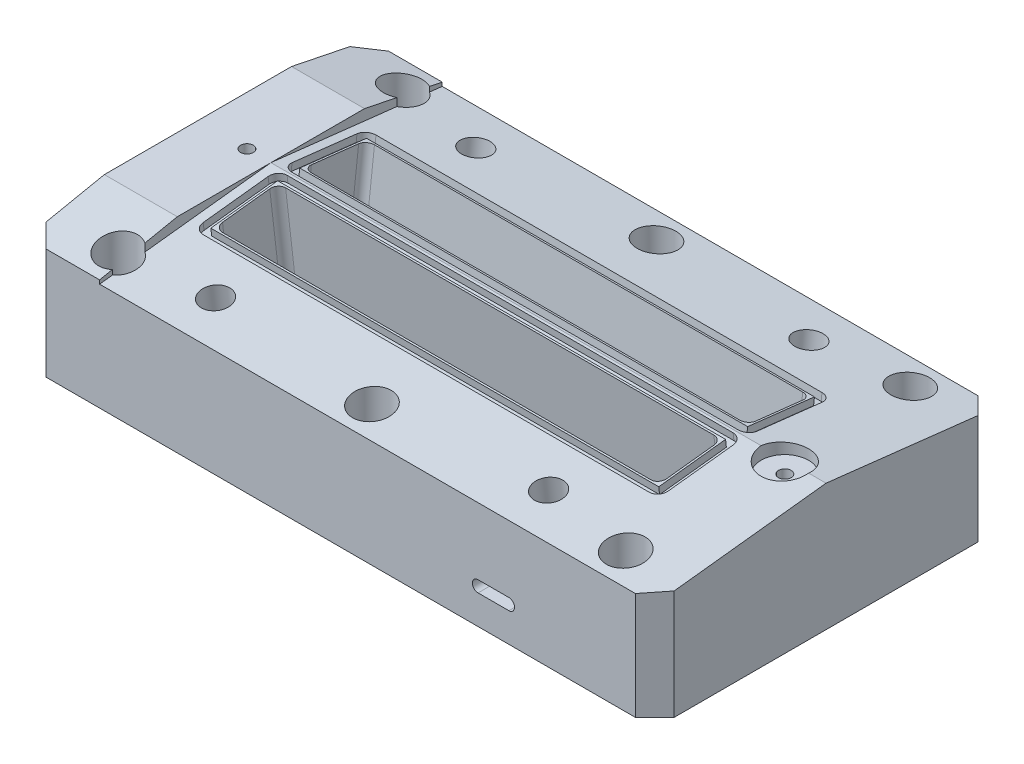
SolidWorks part; units mm, degrees
material "Custom Plastic"
ref_plane "Front Plane" through (0, 0, 0) normal (0, 0, 1) x (1, 0, 0)
ref_plane "Top Plane" through (0, 0, 0) normal (0, 1, 0) x (1, 0, 0)
ref_plane "Right Plane" through (0, 0, 0) normal (1, 0, 0) x (0, 0, -1)
sketch "Sketch1" plane through (0, 0, 0) normal (0, 1, 0) x (1, 0, 0)
  line L1 (0, 0) -> (198, 0)
  line L2 (0, 0) -> (0, 108)
  line L3 (0, 108) -> (198, 108)
  line L4 (198, 0) -> (198, 108)
  dimension "D1" = 198
  dimension "D2" = 108
extrude "Boss-Extrude1" add sketch "Sketch1" along normal blind 40
ref_plane "Left" through (198, 0, 0) normal (1, 0, 0) x (0, 0, -1)
ref_plane "Bot" through (0, 40, 0) normal (0, 1, 0) x (1, 0, 0)
ref_plane "der loco" through (0, 0, -52) normal (0, 0, -1) x (-1, 0, 0)
sketch "Sketch4" plane through (0, 0, 0) normal (0, 1, 0) x (1, 0, 0)
  line L0 (0, 108) -> (0, 0) construction
  line L1 (8.5, 31.5) -> (189.5, 31.5)
  line L2 (8.5, 31.5) -> (8.5, 76.5)
  line L3 (8.5, 76.5) -> (189.5, 76.5)
  line L4 (189.5, 31.5) -> (189.5, 76.5)
  line L5 (0, 0) -> (198, 0) construction
  dimension "D1" = 181
  dimension "D2" = 8.5
  dimension "D3" = 45
  dimension "D4" = 31.5
extrude "Cut-Extrude2" cut sketch "Sketch4" along normal blind 10 contours L2 L1 L4 L3
ref_plane "Plane32" through (0, 10, 0) normal (0, -1, 0) x (-1, 0, 0)
sketch "Sketch5" plane through (198, 0, 0) normal (1, 0, 0) x (0, 0, -1)
  line L0 (54, 40) -> (108, 33.8284)
  line L1 (0, 40) -> (108, 40) construction
  line L2 (108, 33.8284) -> (108, 40)
  line L3 (108, 40) -> (54, 40)
  line L4 (108, 40) -> (108, 0) construction
  dimension "D1" = 6.52
  dimension "D2" = 54
extrude "Cut-Extrude3" cut sketch "Sketch5" against normal blind 175
ref_plane "Plane24" through (0, 10, 0) normal (0, -1, 0) x (-1, 0, 0)
sketch "Sketch53" plane through (0, 10, 0) normal (0, -1, 0) x (-1, 0, 0)
  line L0 (-8.5, 51.5) -> (-8.5, 31.5)
  line L1 (-8.5, 76.5) -> (-8.5, 31.5) construction
  line L2 (-8.5, 31.5) -> (-39.5, 31.5)
  line L3 (-8.5, 31.5) -> (-189.5, 31.5) construction
  line L4 (-39.5, 31.5) -> (-8.5, 51.5)
  line L5 (-8.5, 54) -> (-189.5, 54) construction
  line L6 (-189.5, 31.5) -> (-189.5, 76.5) construction
  line L7 (-8.5, 56.5) -> (-8.5, 76.5)
  line L8 (-8.5, 76.5) -> (-39.5, 76.5)
  line L9 (-39.5, 76.5) -> (-8.5, 56.5)
  line L10 (-99, 76.5) -> (-99, 31.5) construction
  line L11 (-8.5, 76.5) -> (-189.5, 76.5) construction
  line L12 (-8.5, 31.5) -> (-189.5, 31.5) construction
  line L13 (-158.5, 76.5) -> (-189.5, 56.5)
  line L14 (-189.5, 76.5) -> (-158.5, 76.5)
  line L15 (-189.5, 56.5) -> (-189.5, 76.5)
  line L16 (-158.5, 31.5) -> (-189.5, 51.5)
  line L17 (-189.5, 31.5) -> (-158.5, 31.5)
  line L18 (-189.5, 51.5) -> (-189.5, 31.5)
  dimension "D1" = 31
  dimension "D2" = 20
extrude "Boss-Extrude11" add sketch "Sketch53" along normal up to surface (10 mm away) up to face at (99, 0, -54)
ref_plane "izq loco" through (0, 0, -57) normal (0, 0, -1) x (-1, 0, 0)
sketch "Sketch18" plane through (198, 0, 0) normal (1, 0, 0) x (0, 0, -1)
  line L0 (0, 33.8284) -> (0, 40)
  line L1 (0, 40) -> (0, 0) construction
  line L2 (0, 40) -> (54, 40)
  line L3 (54, 40) -> (0, 33.8284)
  line L4 (0, 40) -> (54, 40) construction
  dimension "D1" = 54
  dimension "D2" = 6.52
extrude "Cut-Extrude12" cut sketch "Sketch18" against normal up to surface (175 mm away) up to face at (23, 37.9428, -90)
sketch "Sketch60" plane through (0, 0, 0) normal (0, 1, 0) x (1, 0, 0)
  point P0 (8.5, 31.5)
  point P1 (39.5, 31.5)
  point P2 (8.5, 76.5)
  point P6 (39.5, 76.5)
  dimension "D1" = 20
  dimension "D2" = 31
  dimension "D3" = 20
  dimension "D4" = 31
ref_axis "Axis6" through (8.5, 0, -31.5) along (1, 0, 0)
sketch "Sketch69" plane through (0, 10, 0) normal (0, -1, 0) x (-1, 0, 0)
  point P0 (-39.5, 56.5)
  point P1 (-8.5, 51.5)
  point P2 (-38.5, 51.5)
  point P3 (-8.5, 56.5)
  dimension "D1" = 31
  dimension "D2" = 20
  dimension "D3" = 20
  dimension "D4" = 30
sketch "der loco axis" plane through (0, 0, -52) normal (0, 0, -1) x (-1, 0, 0)
  point P0 (-8.5, 8.5)
  point P1 (-38.5, 8.5)
  dimension "D1" = 1.5
sketch "izq loco axis" plane through (0, 0, -57) normal (0, 0, -1) x (-1, 0, 0)
  line L0 (-39.5, 0) -> (-39.5, 10) construction
  line L1 (-8.5, 0) -> (-8.5, 10) construction
  point P0 (-8.5, 8.4959)
  point P1 (-39.5, 8.4959)
  dimension "D1" = 1.5041
ref_plane "Plane3" through (0, 45.5763, -5.2089) normal (0, 0.9935, -0.1136) x (1, 0, 0)
ref_axis "Axis8" through (39.5, 0, -76.5) along (-1, 0, 0)
ref_axis "Axis9" through (8.5, 8.4959, -57) along (1, 0, 0)
ref_axis "Axis10" through (38.5, 8.5, -52) along (-1, 0, 0)
ref_plane "Izq bueno" through (0, 28.0127, -12.2048) normal (0, 0.9168, -0.3994) x (1, 0, 0)
sketch "Izq" plane through (0, 28.0127, -12.2048) normal (0, 0.9168, -0.3994) x (1, 0, 0)
  line L0 (8.5, 48.8622) -> (29.5, 70.1326)
  line L1 (29.5, 70.1326) -> (8.5, 70.1326)
  line L2 (8.5, 70.1326) -> (8.5, 48.8622)
  dimension "D1" = 21
extrude "Cut-Extrude28" cut sketch "Izq" against normal blind 14.5
ref_plane "Der bueno" through (0, -11.1449, -4.6211) normal (0, 0.9237, 0.383) x (1, 0, 0)
sketch "Der" plane through (0, -11.1449, -4.6211) normal (0, 0.9237, 0.383) x (1, 0, 0)
  line L0 (8.5, 51.2902) -> (29.5, 29.0979)
  line L1 (29.5, 29.0979) -> (8.5, 29.0979)
  line L2 (8.5, 29.0979) -> (8.5, 51.2902)
  dimension "D1" = 21
extrude "Cut-Extrude29" cut sketch "Der" against normal blind 14.5
sketch "Sketch97" plane through (0, 0, 0) normal (0, 1, 0) x (1, 0, 0)
  line L0 (8.5, 57.5) -> (29.5, 76.5)
  line L1 (29.5, 76.5) -> (158.5, 76.5)
  line L3 (158.5, 31.5) -> (29.5, 31.5)
  line L4 (29.5, 31.5) -> (8.5, 51.5)
  line L5 (8.5, 51.5) -> (8.5, 57.5)
  line L7 (158.5, 76.5) -> (189.5, 56.5)
  line L8 (189.5, 56.5) -> (189.5, 51.5)
  line L9 (189.5, 51.5) -> (158.5, 31.5)
  line L10 (39.5, 76.5) -> (158.5, 76.5) construction
  dimension "D1" = 6
extrude "Cut-Extrude40" cut sketch "Sketch97" along normal up to surface (10 mm away) up to face at (99, 10, -54)
ref_axis "Axis11" through (99, 0, -108) along (0, 0, 1)
ref_plane "Plane33" through (99, 0, 0) normal (1, 0, 0) x (0, 0, -1)
mirror "Mirror2" about plane through (99, 0, 0) normal (1, 0, 0) of "Cut-Extrude29", "Cut-Extrude40", "Cut-Extrude28"
sketch "Sketch6" plane through (0, 45.5763, -5.2089) normal (0, 0.9935, -0.1136) x (1, 0, 0)
  line L0 (23, 49.1087) -> (198, 49.1087) construction
  line L1 (28.9, 76.5087) -> (169.5, 76.5087)
  line L2 (25.9, 73.5087) -> (25.9, 52.9087)
  line L3 (28.9, 49.9087) -> (169.5, 49.9087)
  line L4 (172.5, 73.5087) -> (172.5, 52.9087)
  line L7 (28.6, 52.6087) -> (169.8, 52.6087)
  line L8 (28.6, 52.6087) -> (28.6, 73.8087)
  line L9 (28.6, 73.8087) -> (169.8, 73.8087)
  line L10 (169.8, 52.6087) -> (169.8, 73.8087)
  line L13 (198, 49.1087) -> (198, 103.4603) construction
  arc A0 (169.5, 76.5087) -> (172.5, 73.5087) centre (169.5, 73.5087) cw
  arc A1 (169.5, 49.9087) -> (172.5, 52.9087) centre (169.5, 52.9087) ccw
  arc A2 (25.9, 52.9087) -> (28.9, 49.9087) centre (28.9, 52.9087) ccw
  arc A3 (28.9, 76.5087) -> (25.9, 73.5087) centre (28.9, 73.5087) ccw
  dimension "D1" = 3
  dimension "D2" = 146.6
  dimension "D3" = 20.6
  dimension "D4" = 25.5
  dimension "D5" = 3.5
  dimension "D6" = 2.7
  dimension "D7" = 2.7
  dimension "D8" = 2.7
  dimension "D9" = 2.7
sketch "Sketch7" plane through (0, 0, 0) normal (1, 0, 0) x (0, 0, -1)
  line L1 (108, 40) -> (108, 0) construction
  line L2 (108, 40) -> (0, 40) construction
  line L3 (108, 40) -> (108, 35)
  line L5 (108, 35) -> (83.5051, 40)
  line L6 (108, 40) -> (83.5051, 40)
  line L7 (0, 35) -> (0, 40)
  line L8 (0, 40) -> (0, 0) construction
  line L9 (0, 40) -> (24.4949, 40)
  line L10 (24.4949, 40) -> (0, 35)
  dimension "D1" = 25
  dimension "D2" = 35
  dimension "D3" = 35
  dimension "D4" = 25
extrude "Cut-Extrude5" cut sketch "Sketch7" along normal up to vertex (23 mm away) up to point (23, 40, 0)
sketch "Sketch9" plane through (0, 40, 0) normal (0, 1, 0) x (1, 0, 0)
  line L0 (0, 83.5051) -> (0, 24.4949) construction
  circle A0 centre (15.45, 54) radius 8
  point P6 (0, 54)
  dimension "D1" = 16
  dimension "D2" = 15.45
sketch "Sketch12" plane through (0, 40, 0) normal (0, 1, 0) x (1, 0, 0)
  line L0 (0, 83.5051) -> (0, 108) construction
  line L2 (23, 108) -> (0, 108) construction
  line L3 (23, 0) -> (0, 0) construction
  circle A0 centre (19.7, 98.85) radius 3.15
  circle A1 centre (99.7, 9.15) radius 3.15
  circle A2 centre (179.7, 9.15) radius 3.15
  circle A3 centre (19.7, 9.15) radius 3.15
  circle A4 centre (99.7, 98.85) radius 3.15
  circle A5 centre (179.7, 98.85) radius 3.15
  dimension "D2" = 6.3
  dimension "D3" = 19.7
  dimension "D7" = 80
  dimension "D9" = 80
  dimension "D10" = 9.15
  dimension "D11" = 9.15
extrude "Cut-Extrude9" cut sketch "Sketch12" against normal through all
sketch "Sketch13" plane through (0, 45.5763, -5.2089) normal (0, 0.9935, -0.1136) x (1, 0, 0)
  line L0 (23, 49.1087) -> (23, 103.4603) construction
  line L1 (23, 103.4603) -> (198, 103.4603) construction
  line L2 (198, 49.1087) -> (198, 103.4603) construction
  circle A0 centre (46.5, 90.4603) radius 4.5
  circle A1 centre (151.5, 90.4603) radius 4.5
  dimension "D1" = 9
  dimension "D4" = 9
  dimension "D2" = 23.5
  dimension "D3" = 13
  dimension "D5" = 46.5
extrude "Cut-Extrude10" cut sketch "Sketch13" against normal blind 16.5
ref_plane "Plane8" through (0, 33.6, 6.8586) normal (0, 0.9798, 0.2) x (1, 0, 0)
sketch "Sketch14" plane through (0, 33.0588, 6.7339) normal (0, 0.9935, 0.1136) x (1, 0, 0)
  line L0 (23, 6.9107) -> (0, 6.9107) construction
  line L1 (23, 61.1292) -> (23, 114.0792) construction
  line L2 (198, 6.9107) -> (198, 31.815) construction
  circle A0 centre (46.5, 19.9107) radius 4.5
  circle A1 centre (151.5, 19.9107) radius 4.5
  dimension "D1" = 9
  dimension "D2" = 9
  dimension "D3" = 13
  dimension "D4" = 23.5
  dimension "D5" = 46.5
extrude "Cut-Extrude11" cut sketch "Sketch14" against normal blind 16.5
ref_plane "Plane9" through (0, 33.3922, 3.8164) normal (0, 0.9935, 0.1136) x (1, 0, 0)
sketch "Sketch23" plane through (0, 33.3922, 3.8164) normal (0, 0.9935, 0.1136) x (1, 0, 0)
  line L0 (23, 58.1927) -> (198, 58.1927) construction
  line L1 (28.9, 57.3927) -> (169.5, 57.3927)
  line L2 (25.9, 54.3927) -> (25.9, 33.7927)
  line L3 (28.9, 30.7927) -> (169.5, 30.7927)
  line L4 (172.5, 54.3927) -> (172.5, 33.7927)
  line L7 (28.6, 54.6927) -> (169.8, 54.6927)
  line L8 (28.6, 54.6927) -> (28.6, 33.4927)
  line L9 (28.6, 33.4927) -> (169.8, 33.4927)
  line L10 (169.8, 54.6927) -> (169.8, 33.4927)
  line L12 (198, 3.8412) -> (198, 58.1927) construction
  arc A0 (169.5, 57.3927) -> (172.5, 54.3927) centre (169.5, 54.3927) cw
  arc A1 (169.5, 30.7927) -> (172.5, 33.7927) centre (169.5, 33.7927) ccw
  arc A2 (25.9, 33.7927) -> (28.9, 30.7927) centre (28.9, 33.7927) ccw
  arc A3 (28.9, 57.3927) -> (25.9, 54.3927) centre (28.9, 54.3927) ccw
  point P10 (172.5, 57.3927)
  point P15 (25.9, 30.7927)
  point P18 (25.9, 57.3927)
  dimension "D5" = 3
  dimension "D1" = 146.6
  dimension "D2" = 20.6
  dimension "D3" = 3.5
  dimension "D4" = 25.5
  dimension "D6" = 2.7
  dimension "D7" = 2.7
  dimension "D8" = 2.7
  dimension "D9" = 2.7
sketch "Sketch41" plane through (0, 0, 0) normal (0, 1, 0) x (1, 0, 0)
  line L0 (198, 0) -> (198, 108) construction
  line L1 (198, 108) -> (0, 108) construction
  line L2 (0, 0) -> (198, 0) construction
  circle A0 centre (139.5, 9) radius 2.9
  circle A1 centre (139.5, 99) radius 2.9
  dimension "D1" = 5.8
  dimension "D4" = 5.8
  dimension "D2" = 58.5
  dimension "D3" = 58.5
  dimension "D5" = 9
  dimension "D6" = 9
extrude "Cut-Extrude21" cut sketch "Sketch41" along normal blind 7
sketch "Sketch42" plane through (0, 0, 0) normal (0, 0, 1) x (1, 0, 0)
  line L0 (198, 33.8284) -> (198, 0) construction
  line L5 (0, 0) -> (198, 0) construction
  line L6 (142.3, 12.8) -> (152, 12.8)
  line L7 (142.3, 9.2) -> (152, 9.2)
  arc A0 (142.3, 12.8) -> (142.3, 9.2) centre (142.3, 11) ccw
  arc A2 (152, 12.8) -> (152, 9.2) centre (152, 11) cw
  dimension "D2" = 1.8
  dimension "D3" = 1.8
  dimension "D1" = 9.7
  dimension "D5" = 46
  dimension "D6" = 11
extrude "Cut-Extrude22" cut sketch "Sketch42" against normal blind 10
ref_plane "Plane19" through (0, 0, -108) normal (0, 0, -1) x (-1, 0, 0)
sketch "Sketch43" plane through (0, 0, -108) normal (0, 0, -1) x (-1, 0, 0)
  line L0 (-55.7, 11) -> (-46, 11) construction
  line L1 (-55.7, 12.8) -> (-46, 12.8)
  line L2 (-55.7, 9.2) -> (-46, 9.2)
  line L3 (-198, 0) -> (0, 0) construction
  line L4 (0, 35) -> (0, 0) construction
  arc A0 (-55.7, 12.8) -> (-55.7, 9.2) centre (-55.7, 11) ccw
  arc A1 (-46, 9.2) -> (-46, 12.8) centre (-46, 11) ccw
  point P2 (-50.85, 11)
  dimension "D2" = 1.8
  dimension "D1" = 9.7
  dimension "D3" = 11
  dimension "D4" = 46
extrude "Cut-Extrude23" cut sketch "Sketch43" against normal blind 10
extrude "Cut-Extrude32" cut sketch "Sketch6" against normal blind 2.3
extrude "Cut-Extrude33" cut sketch "Sketch23" against normal blind 2.3
sketch "Sketch83" plane through (0, 33.3922, 3.8164) normal (0, 0.9935, 0.1136) x (1, 0, 0)
  line L0 (28.6, 54.6927) -> (28.6, 33.4927) construction
  line L1 (31.7, 54.0927) -> (166.7, 54.0927)
  line L2 (29.2, 51.5927) -> (29.2, 36.5927)
  line L3 (31.7, 34.0927) -> (166.7, 34.0927)
  line L4 (169.2, 51.5927) -> (169.2, 36.5927)
  line L5 (169.8, 54.6927) -> (28.6, 54.6927) construction
  arc A0 (166.7, 34.0927) -> (169.2, 36.5927) centre (166.7, 36.5927) ccw
  arc A1 (166.7, 54.0927) -> (169.2, 51.5927) centre (166.7, 51.5927) cw
  arc A2 (29.2, 36.5927) -> (31.7, 34.0927) centre (31.7, 36.5927) ccw
  arc A3 (31.7, 54.0927) -> (29.2, 51.5927) centre (31.7, 51.5927) ccw
  point P12 (169.2, 54.0927)
  point P15 (29.2, 34.0927)
  point P18 (29.2, 54.0927)
  point P19 (169.2, 44.0927)
  dimension "D5" = 2.5
  dimension "D1" = 140
  dimension "D2" = 20
  dimension "D3" = 0.6
  dimension "D4" = 0.6
extrude "Cut-Extrude34" cut sketch "Sketch83" against normal blind 55.4
sketch "Sketch84" plane through (0, 45.5763, -5.2089) normal (0, 0.9935, -0.1136) x (1, 0, 0)
  line L1 (31.7, 53.2087) -> (166.7, 53.2087)
  line L2 (29.2, 55.7087) -> (29.2, 70.7087)
  line L3 (31.7, 73.2087) -> (166.7, 73.2087)
  line L4 (169.2, 55.7087) -> (169.2, 70.7087)
  line L6 (169.8, 52.6087) -> (169.8, 73.8087) construction
  line L8 (28.6, 52.6087) -> (169.8, 52.6087) construction
  arc A0 (166.7, 53.2087) -> (169.2, 55.7087) centre (166.7, 55.7087) ccw
  arc A1 (166.7, 73.2087) -> (169.2, 70.7087) centre (166.7, 70.7087) cw
  arc A2 (29.2, 70.7087) -> (31.7, 73.2087) centre (31.7, 70.7087) cw
  arc A3 (31.7, 53.2087) -> (29.2, 55.7087) centre (31.7, 55.7087) cw
  point P10 (169.2, 53.2087)
  point P13 (169.2, 73.2087)
  point P16 (29.2, 73.2087)
  point P19 (169.2, 63.2087)
  dimension "D5" = 2.5
  dimension "D1" = 140
  dimension "D2" = 20
  dimension "D3" = 0.6
  dimension "D4" = 0.6
extrude "Cut-Extrude35" cut sketch "Sketch84" against normal blind 55.4
sketch "Sketch85" plane through (0, 40, 0) normal (0, 1, 0) x (1, 0, 0)
  line L0 (0, 101.9) -> (6.1, 108)
  line L1 (0, 83.5051) -> (0, 108) construction
  line L2 (23, 108) -> (0, 108) construction
  line L3 (6.1, 108) -> (0, 108)
  line L4 (0, 108) -> (0, 101.9)
  line L5 (0, 0) -> (6.1, 0)
  line L6 (23, 0) -> (0, 0) construction
  line L7 (6.1, 0) -> (0, 6.1)
  line L8 (0, 0) -> (0, 24.4949) construction
  line L9 (0, 6.1) -> (0, 0)
  line L10 (198, 6.1) -> (191.9, 0)
  line L11 (198, 0) -> (198, 54) construction
  line L12 (23, 0) -> (198, 0) construction
  line L13 (191.9, 0) -> (198, 0)
  line L14 (198, 0) -> (198, 6.1)
  line L15 (198, 108) -> (191.9, 108)
  line L16 (23, 108) -> (198, 108) construction
  line L17 (191.9, 108) -> (198, 101.9)
  line L18 (198, 54) -> (198, 108) construction
  line L19 (198, 101.9) -> (198, 108)
  dimension "D1" = 6.1
  dimension "D2" = 6.1
  dimension "D3" = 6.1
  dimension "D4" = 6.1
  dimension "D5" = 6.1
  dimension "D6" = 6.1
  dimension "D7" = 6.1
extrude "Cut-Extrude36" cut sketch "Sketch85" against normal blind 55.4
sketch "Sketch90" plane through (0, 40, 0) normal (0, 1, 0) x (1, 0, 0)
  circle A0 centre (19.7, 9.15) radius 6.1
  circle A1 centre (99.7, 9.15) radius 6.1
  circle A2 centre (179.7, 9.15) radius 6.1
  circle A3 centre (99.7, 98.85) radius 6.1
  circle A4 centre (179.7, 98.85) radius 6.1
  circle A5 centre (19.7, 98.85) radius 6.1
  circle A6 centre (179.7, 98.85) radius 3.15 construction
  circle A7 centre (99.7, 98.85) radius 3.15 construction
  dimension "D1" = 12.2
  dimension "D2" = 3
  dimension "D3" = 2
extrude "Cut-Extrude38" cut sketch "Sketch90" against normal blind 17
sketch "Sketch96" plane through (0, 0, 0) normal (0, 1, 0) x (1, 0, 0)
  line L0 (23, 54) -> (198, 54) construction
  line L1 (198, 6.1) -> (198, 101.9) construction
  circle A0 centre (15.45, 54) radius 2
  circle A1 centre (185, 54) radius 2
  dimension "D1" = 4
  dimension "D2" = 4
  dimension "D3" = 13
extrude "Cut-Extrude39" cut sketch "Sketch96" along normal through all
sketch "Sketch98" plane through (0, 40, 0) normal (0, 1, 0) x (1, 0, 0)
  circle A0 centre (185, 54) radius 7.5
  dimension "D1" = 15
extrude "Cut-Extrude41" cut sketch "Sketch98" against normal blind 4
sketch "Sketch99" plane through (198, 0, 0) normal (1, 0, 0) x (0, 0, -1)
  line L0 (57.4774, 39.6026) -> (78.5402, 37.1953) construction
  line L1 (54, -84.21) -> (68.0088, 38.3989) construction
  line L2 (54, -84.21) -> (123.3982, -92.1415) construction
  line L3 (54, 40) -> (101.9, 34.5255) construction
  line L4 (54, -84.21) -> (-15.3982, -92.1415) construction
  line L5 (6.1, 34.5255) -> (54, 40) construction
  line L6 (54.0041, -84.21) -> (39.9912, 38.3989) construction
  line L7 (-15.85, -84.21) -> (123.85, -84.21) construction
  line L8 (54, -84.21) -> (39.9912, 38.3989) construction
  line L9 (32.5397, 37.5473) -> (47.4427, 39.2506) construction
  line L10 (53.9959, -84.21) -> (68.0088, 38.3989) construction
  line L11 (6.1, 0) -> (101.9, 0) construction
  line L12 (54, -103.26) -> (142.325, -113.3546) construction
  line L13 (54, -103.26) -> (-34.325, -113.3546) construction
  line L14 (175.4469, -150.4776) -> (54, -136.5975) construction
  line L15 (68.0088, 38.3989) -> (54, -103.26) construction
  line L16 (54, -136.5975) -> (-67.4469, -150.4776) construction
  line L17 (68.0088, 38.3989) -> (54, -136.5975) construction
  circle A0 centre (54, -84.21) radius 69.85
  circle A1 centre (54, -103.26) radius 88.9
  circle A2 centre (54, -136.5975) radius 122.2375
  circle A3 centre (54, -58.81) radius 44.45
  point P19 (39.9912, 38.3989)
  dimension "D1" = 139.7
  dimension "D6" = 177.8
  dimension "D7" = 103.26
  dimension "D8" = 244.475
  dimension "D10" = 88.9
  dimension "D2" = 84.21
  dimension "D3" = 90.002
  dimension "D4" = 90.002
  dimension "D5" = 90.872
  dimension "D9" = 91.943
sketch "Sketch100" plane through (198, 0, 0) normal (1, 0, 0) x (0, 0, -1)
  line L0 (16, 40) -> (16, 35.657)
  line L1 (6.1, 34.5255) -> (54, 40) construction
  line L2 (16, 35.657) -> (54, 40)
  line L3 (54, 40) -> (93.7197, 35.4605) construction
  line L4 (54, 40) -> (16, 40)
  dimension "D1" = 16
extrude "Cut-Extrude42" [suppressed] cut sketch "Sketch100" against normal blind 175
sketch "Sketch101" plane through (198, 0, 0) normal (1, 0, 0) x (0, 0, -1)
  line L0 (54, 40) -> (83.5051, 40)
  line L1 (83.5051, 40) -> (83.5051, 36.6279)
  line L2 (103.9803, 34.2878) -> (108, 33.8284) construction
  line L3 (83.5051, 36.6279) -> (54, 40)
extrude "Cut-Extrude43" [suppressed] cut sketch "Sketch101" against normal blind 175
